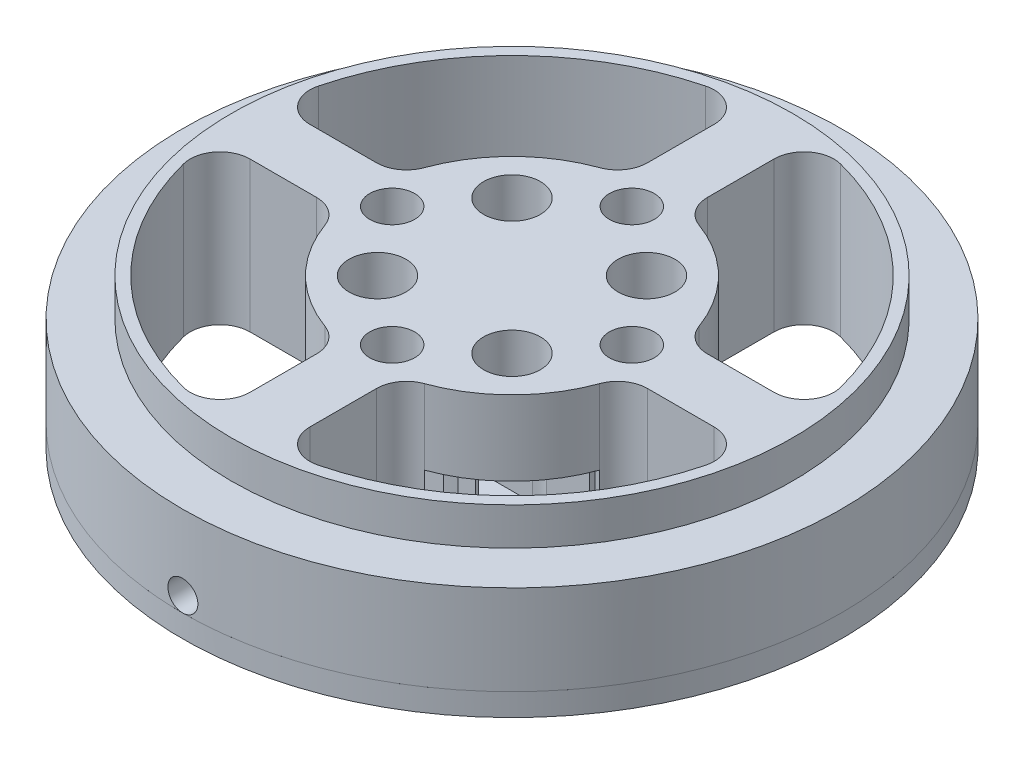
SolidWorks part; units mm, degrees
note: '?' marks a value the reader was unsure of.
ref_plane "Front Plane" through (0, 0, 0) normal (0, 0, 1) x (1, 0, 0)
ref_plane "Top Plane" through (0, 0, 0) normal (0, 1, 0) x (1, 0, 0)
ref_plane "Right Plane" through (0, 0, 0) normal (1, 0, 0) x (0, 0, -1)
ref_axis "Axis1" through (0, 10.5, 0) along (0, -1, 0)?
sketch "Sketch1" plane through (0, 0, 0) normal (0, 1, 0) x (1, 0, 0)
  line L0 (0, 22) -> (0, -22) construction
  line L1 (-22, 0) -> (22, 0) construction
  line L2 (-2, 22) -> (-2, -22)
  line L3 (2, 22) -> (2, -22)
  line L4 (-22, -2) -> (22, -2)
  line L5 (-22, 2) -> (22, 2)
  circle A0 centre (0, 0) radius 22
  circle A1 centre (0, 0) radius 9.75
  circle A2 centre (0, 0) radius 18
  dimension "D1" = 44
  dimension "D2" = 19.5
  dimension "D7" = 4
  dimension "D3" = 2
  dimension "D4" = 2
  dimension "D5" = 2
  dimension "D6" = 2
extrude "Boss-Extrude1" add sketch "Sketch1" along normal blind 10 contours A2 L3 A0 L4 | A2 L2 A0 L3 | A2 L4 A0 L2 | A2 L5 A0 L4 | A2 L2 A0 L5 | A2 L3 A0 L2 | A2 L5 A0 L3 | A2 L4 A0 L5 | L3 A2 L2 A1 | L4 A1 L5 L3 | L2 A1 L3 L4 | L2 A2 L3 A1 | L4 A2 L5 A1 | L3 A1 L4 | L4 A1 L2 | L5 A1 L4 L2 | L5 A2 L4 A1 | L3 A1 L2 L5 | L5 L2 L4 L3 | L5 A1 L3 | L2 A1 L5
fillet "Fillet1" radius 2 16 edges at (-2, 5, 17.8885) (-2, 5, -17.8885) (17.8885, 5, -2) (-17.8885, 5, -2) (9.5427, 5, -2) (-9.5427, 5, -2) (-2, 5, 9.5427) (-2, 5, -9.5427) (2, 5, 9.5427) (2, 5, -9.5427) (2, 5, 17.8885) (2, 5, -17.8885) (17.8885, 5, 2) (-17.8885, 5, 2) (9.5427, 5, 2) (-9.5427, 5, 2)
sketch "Sketch2" plane through (0, 0, 0) normal (0, -1, 0) x (1, 0, 0)
  line L0 (0, 0) -> (0, 22) construction
  line L1 (0, 23.2273) -> (0, 21.9773) construction
  line L2 (-1, 23.2273) -> (1, 23.2273)
  line L3 (-1, 23.2273) -> (-1, 21.9773)
  line L4 (-1, 21.9773) -> (1, 21.9773)
  line L5 (1, 23.2273) -> (1, 21.9773)
  circle A1 centre (0, 0) radius 22 construction
  circle A2 centre (0, 0) radius 22
  circle M9 centre (0, 0) radius 22
  dimension "D1" = 1.25
  dimension "D2" = 2
extrude "Boss-Extrude2" add sketch "Sketch2" against normal blind 1.5 contours L5 L2 L3 M9
fillet "Fillet2" radius 2 2 edges at (-1, 0.75, 21.9773) (1, 0.75, 21.9773)
pattern_circular "CirPattern1" count 26 over 360 about axis through (0, 0, 0) along (0, 1, 0) of "Boss-Extrude2", "Fillet2"
sketch "Sketch3" plane through (0, 10, 0) normal (0, 1, 0) x (1, 0, 0)
  line L0 (0, 0) -> (0, 23.2273) construction
  line L1 (0, 0) -> (5.5586, 22.5523) construction
  line L4 (1, 23.2273) -> (-1, 23.2273) construction
  line L5 (6.5296, 22.313) -> (4.5877, 22.7916) construction
  line L6 (4.2993, 19.5324) -> (3.5098, 18.4186)
  line L7 (2.6368, 21.8414) -> (0, 0) construction
  line L8 (0.4726, 19.9944) -> (0.9743, 18.7247)
  line L9 (0, 22) -> (0, 20)
  line L10 (4.7863, 19.4188) -> (5.2649, 21.3607)
  circle A2 centre (0, 0) radius 22
  circle A3 centre (0, 0) radius 22 construction
  circle A4 centre (0, 0) radius 20
  circle A5 centre (0, 0) radius 18.75
  circle M17 centre (0, 0) radius 22
  dimension "D1" = 2
  dimension "D2" = 3.25
  dimension "D3" = 1
  dimension "D4" = 2
extrude "Cut-Extrude1" cut sketch "Sketch3" against normal blind 2.5 contours A4 L10 L9 M17 | A5 L6 A4 L8
fillet "Fillet3" radius 2 2 edges at (3.5098, 8.75, -18.4186) (0.9743, 8.75, -18.7247)
pattern_circular "CirPattern2" count 26 over 360 about axis through (0, 0, 0) along (0, 1, 0) of "Cut-Extrude1", "Fillet3"
sketch "Sketch4" plane through (0, 10, 0) normal (0, 1, 0) x (1, 0, 0)
  line L0 (0, 22) -> (0, -22) construction
  line L1 (-22.0001, 0) -> (22, 0) construction
  line L2 (-8, 0) -> (0, 0) construction
  line L3 (-8, 1.5) -> (0, 1.5) construction
  line L4 (-1.5, 8) -> (-1.5, 0) construction
  circle A0 centre (0, 0) radius 22 construction
  arc A1 (2.6368, 21.8414) -> (-2.6668, 21.8378) centre (0, 0) ccw construction
  circle A2 centre (0, 8) radius 1.5
  circle A3 centre (0, -8) radius 1.5
  circle A4 centre (-8, 0) radius 1.5
  circle A5 centre (8, 0) radius 1.5
  dimension "D1" = 3
  dimension "D2" = 8
extrude "Cut-Extrude2" cut sketch "Sketch4" against normal blind 2.75
sketch "Sketch5" [suppressed] plane through (0, 0, 0) normal (0, -1, 0) x (1, 0, 0)
  circle A0 centre (0, 0) radius 2.15
  dimension "D1" = 4.3
extrude "Cut-Extrude3" [suppressed] cut sketch "Sketch5" against normal up to next
sketch "Sketch6" [suppressed] plane through (0, 0, 0) normal (0, -1, 0) x (1, 0, 0)
  circle A0 centre (0, 0) radius 2.7
  dimension "D1" = 5.4
extrude "Cut-Extrude4" [suppressed] cut sketch "Sketch6" against normal blind 4.35
sketch "Sketch7" [suppressed] plane through (0, 0, 0) normal (0, -1, 0) x (1, 0, 0)
  line L0 (-22.0001, 0) -> (22.0001, 0) construction
  line L2 (-5.125, 1.125) -> (5.125, 1.125)
  line L3 (-5.125, 1.125) -> (-5.125, -1.125)
  line L4 (-5.125, -1.125) -> (5.125, -1.125)
  line L5 (5.125, 1.125) -> (5.125, -1.125)
  line L6 (-5.125, 1.125) -> (5.125, -1.125) construction
  line L7 (-5.125, -1.125) -> (5.125, 1.125) construction
  point P4 (0, 0)
  dimension "D1" = 10.25
  dimension "D2" = 2.25
extrude "Cut-Extrude5" [suppressed] cut sketch "Sketch7" against normal blind 3
sketch "Sketch8" plane through (0, 0, 0) normal (0, -1, 0) x (1, 0, 0)
  circle A0 centre (0, 0) radius 9.75
  arc A1 (9.1676, 3.3191) -> (3.3191, 9.1676) centre (0, 0) ccw construction
extrude "Cut-Extrude6" cut sketch "Sketch8" against normal blind 5
sketch "Sketch9" plane through (0, 5, 0) normal (0, -1, 0) x (1, 0, 0)
  line L0 (-1.4142, 1.75) -> (1.4142, 1.75)
  line L1 (0, -2.25) -> (0, 2.25) construction
  circle A0 centre (0, 0) radius 2.25
  dimension "D1" = 4.5
  dimension "D2" = 4
extrude "Cut-Extrude7" cut sketch "Sketch9" against normal blind 3 contours L1 A0 L0 | A0 L1 L0
sketch "Sketch10" plane through (0, 5, 0) normal (0, -1, 0) x (1, 0, 0)
  line L0 (0, 0) -> (6.8943, 6.8943) construction
  line L1 (0, 6.35) -> (0, -6.35) construction
  line L2 (-6.35, 0) -> (6.35, 0) construction
  circle A0 centre (0, 0) radius 6.35
  arc A1 (9.1676, 3.3191) -> (3.3191, 9.1676) centre (0, 0) ccw construction
  circle A2 centre (4.4901, 4.4901) radius 1.9
  circle A3 centre (-4.4901, 4.4901) radius 1.9
  circle A4 centre (4.4901, -4.4901) radius 1.9
  circle A5 centre (-4.4901, -4.4901) radius 1.9
  dimension "D1" = 12.7
  dimension "D2" = 3.8
extrude "Cut-Extrude8" cut sketch "Sketch10" against normal up to next contours A3 A0 | A3 A0 | A0 A2 | A0 A2 | A4 A0 | A4 A0 | A0 A5 | A0 A5
ref_plane "Plane1" through (0, 0, 22) normal (0, 0, 1) x (1, 0, 0)
sketch "Sketch11" plane through (0, 0, 22) normal (0, 0, 1) x (1, 0, 0)
  line L0 (0, 0) -> (0.0137, 10) construction
  line L1 (0.5, 10) -> (-0.4726, 10) construction
  circle A0 centre (0.0034, 2.5) radius 1
  dimension "D1" = 2.5
  dimension "D2" = 2
extrude "Cut-Extrude9" cut sketch "Sketch11" against normal up to next
sketch "Sketch12" plane through (0, 5, 0) normal (0, -1, 0) x (1, 0, 0)
  line L0 (-8.25, -2.35) -> (-8.25, -2.65)
  line L1 (-8.25, 0.15) -> (8.25, 0.15)
  line L2 (-8.25, 0.15) -> (-8.25, -0.15)
  line L3 (-8.25, -0.15) -> (8.25, -0.15)
  line L4 (8.25, 0.15) -> (8.25, -0.15)
  line L5 (-8.25, 0.15) -> (8.25, -0.15) construction
  line L6 (-8.25, -0.15) -> (8.25, 0.15) construction
  line L7 (-8.25, -2.65) -> (8.25, -2.65)
  line L8 (-8.25, -2.35) -> (8.25, -2.35)
  line L9 (8.25, -2.35) -> (8.25, -2.65)
  line L10 (-8.25, -4.85) -> (-8.25, -5.15)
  line L11 (-8.25, -5.15) -> (8.25, -5.15)
  line L12 (-8.25, -4.85) -> (8.25, -4.85)
  line L13 (8.25, -4.85) -> (8.25, -5.15)
  line L14 (-8.25, -7.35) -> (-8.25, -7.65)
  line L15 (-8.25, -7.65) -> (8.25, -7.65)
  line L16 (-8.25, -7.35) -> (8.25, -7.35)
  line L17 (8.25, -7.35) -> (8.25, -7.65)
  line L18 (-8.25, 0.15) -> (-8.25, -0.15)
  line L19 (-8.25, -0.15) -> (8.25, -0.15)
  line L20 (-8.25, 0.15) -> (8.25, 0.15)
  line L21 (8.25, 0.15) -> (8.25, -0.15)
  line L22 (-8.25, -2.35) -> (-8.25, -2.65)
  line L23 (-8.25, -2.65) -> (8.25, -2.65)
  line L24 (-8.25, -2.35) -> (8.25, -2.35)
  line L25 (8.25, -2.35) -> (8.25, -2.65)
  line L26 (-8.25, -4.85) -> (-8.25, -5.15)
  line L27 (-8.25, -5.15) -> (8.25, -5.15)
  line L28 (-8.25, -4.85) -> (8.25, -4.85)
  line L29 (8.25, -4.85) -> (8.25, -5.15)
  line L30 (-8.25, 2.65) -> (-8.25, 2.35)
  line L31 (-8.25, 2.35) -> (8.25, 2.35)
  line L32 (-8.25, 2.65) -> (8.25, 2.65)
  line L33 (8.25, 2.65) -> (8.25, 2.35)
  line L34 (-8.25, 0.15) -> (-8.25, -0.15)
  line L35 (-8.25, -0.15) -> (8.25, -0.15)
  line L36 (-8.25, 0.15) -> (8.25, 0.15)
  line L37 (8.25, 0.15) -> (8.25, -0.15)
  line L38 (-8.25, -2.35) -> (-8.25, -2.65)
  line L39 (-8.25, -2.65) -> (8.25, -2.65)
  line L40 (-8.25, -2.35) -> (8.25, -2.35)
  line L41 (8.25, -2.35) -> (8.25, -2.65)
  line L42 (-8.25, 5.15) -> (-8.25, 4.85)
  line L43 (-8.25, 4.85) -> (8.25, 4.85)
  line L44 (-8.25, 5.15) -> (8.25, 5.15)
  line L45 (8.25, 5.15) -> (8.25, 4.85)
  line L46 (-8.25, 2.65) -> (-8.25, 2.35)
  line L47 (-8.25, 2.35) -> (8.25, 2.35)
  line L48 (-8.25, 2.65) -> (8.25, 2.65)
  line L49 (8.25, 2.65) -> (8.25, 2.35)
  line L50 (-8.25, 0.15) -> (-8.25, -0.15)
  line L51 (-8.25, -0.15) -> (8.25, -0.15)
  line L52 (-8.25, 0.15) -> (8.25, 0.15)
  line L53 (8.25, 0.15) -> (8.25, -0.15)
  line L54 (-8.25, 2.65) -> (-8.25, 2.35)
  line L55 (-8.25, 2.35) -> (8.25, 2.35)
  line L56 (-8.25, 2.65) -> (8.25, 2.65)
  line L57 (8.25, 2.65) -> (8.25, 2.35)
  line L58 (-8.25, 5.15) -> (-8.25, 4.85)
  line L59 (-8.25, 4.85) -> (8.25, 4.85)
  line L60 (-8.25, 5.15) -> (8.25, 5.15)
  line L61 (8.25, 5.15) -> (8.25, 4.85)
  line L62 (-8.25, 7.65) -> (-8.25, 7.35)
  line L63 (-8.25, 7.35) -> (8.25, 7.35)
  line L64 (-8.25, 7.65) -> (8.25, 7.65)
  line L65 (8.25, 7.65) -> (8.25, 7.35)
  circle A0 centre (0, 0) radius 8.25
  circle A1 centre (4.4901, -4.4901) radius 1.9 construction
  point P0 (0, 0)
  point P9 (8.25, 0)
  dimension "D2" = 4
  dimension "D1" = 0.3
  dimension "D3" = 4
extrude "Boss-Extrude3" add sketch "Sketch12" along normal up to surface (5 mm away)
sketch "Sketch13" plane through (0, 0, 0) normal (0, -1, 0) x (1, 0, 0)
  circle A0 centre (0, 0) radius 8.25
  arc A1 (-8.2486, 0.15) -> (-8.2486, -0.15) centre (0, 0) ccw construction
extrude "Boss-Extrude4" add sketch "Sketch13" against normal blind 0.2
sketch "Sketch14" plane through (0, 10, 0) normal (0, 1, 0) x (1, 0, 0)
  circle A0 centre (0, 0) radius 20
  arc A1 (0.4726, 19.9944) -> (-0.5, 19.9937) centre (0, 0) ccw construction
  circle A2 centre (0, 0) radius 18.75
extrude "Cut-Extrude10" cut sketch "Sketch14" against normal up to surface (2.5 mm away) up to face at (0, 7.5, 22)
sketch "Sketch15" plane through (0, 0, 0) normal (0, -1, 0) x (1, 0, 0)
  circle A0 centre (0, 0) radius 23.2488
  circle A1 centre (0, 0) radius 22.0001
extrude "Cut-Extrude11" cut sketch "Sketch15" against normal up to next
